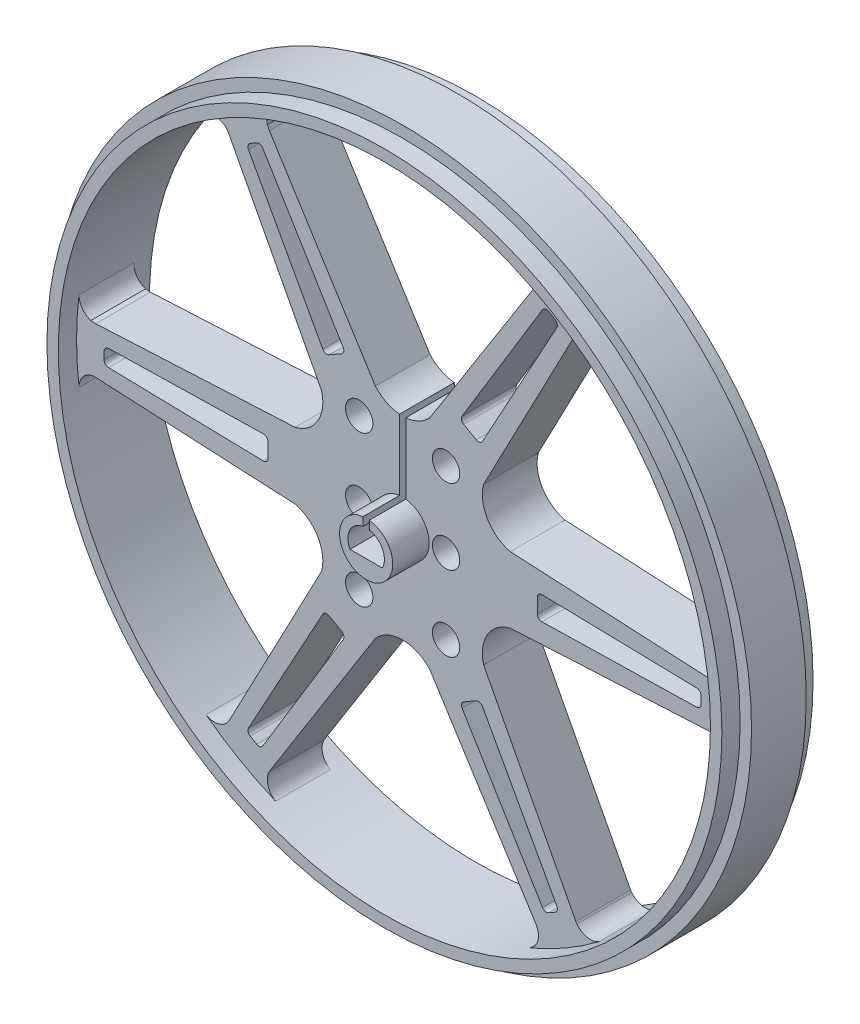
SolidWorks part; units mm, degrees
material "ABS"
ref_plane "Ön Düzlem" through (0, 0, 0) normal (0, 0, 1) x (1, 0, 0)
ref_plane "Üst Düzlem" through (0, 0, 0) normal (0, 1, 0) x (1, 0, 0)
ref_plane "Sağ Düzlem" through (0, 0, 0) normal (1, 0, 0) x (0, 0, -1)
sketch "Çizim1" plane through (0, 0, 0) normal (0, 0, 1) x (1, 0, 0)
  line L1 (-0.0047, 8.2114) -> (0.3453, 8.2114)
  line L2 (-0.0047, 8.2114) -> (-0.3547, 8.2115)
  line L3 (0.3453, 10.6198) -> (0.3453, 1.97)
  line L4 (-0.3399, 10.62) -> (-0.3443, 1.9701)
  line L5 (-1.771, -0.9293) -> (1.771, -0.9293)
  line L6 (33.6573, 2.4999) -> (33.8491, 2.5141)
  line L7 (33.6573, -2.4999) -> (33.8491, -2.5141)
  line L9 (18.994, -27.8979) -> (19.1072, -28.0642)
  line L16 (-33.6536, -2.5496) -> (-34.1903, -2.5903)
  line L17 (-33.6536, 2.5496) -> (-34.1903, 2.5903)
  line L18 (-19.3245, 28.3019) -> (-19.0457, 27.8638)
  line L19 (-14.8479, 30.8484) -> (-14.6079, 30.3879)
  line L21 (14.6633, 30.3602) -> (14.6637, 30.3599)
  line L24 (18.994, 27.8979) -> (18.9936, 27.8981)
  line L36 (-19.0457, 27.8638) -> (-8.8869, 8.5771)
  line L37 (-14.6079, 30.3879) -> (-2.985, 11.9466)
  line L39 (14.6633, 30.3602) -> (2.991, 11.9451)
  line L40 (18.994, 27.8979) -> (8.883, 8.5811)
  line L41 (33.6573, 2.4999) -> (11.8039, 3.6347)
  line L42 (33.6573, -2.4999) -> (11.8043, -3.6332)
  line L43 (8.8819, -8.5822) -> (18.994, -27.8979)
  line L44 (2.9911, -11.9832) -> (14.6637, -30.398)
  line L45 (-2.9849, -11.9847) -> (-14.6079, -30.426)
  line L46 (-8.8883, -8.5756) -> (-19.0457, -27.8638)
  line L47 (-11.8026, -3.6389) -> (-33.6536, -2.5496)
  line L48 (-11.8008, 3.6448) -> (-33.6536, 2.5496)
  line L49 (32.7268, 0.411) -> (32.7268, -0.411)
  line L50 (32.2379, 0.9109) -> (15.2736, 1.2886)
  line L51 (14.7625, 0.7887) -> (14.7625, -0.7887)
  line L52 (32.2379, -0.9109) -> (15.2736, -1.2886)
  line L53 (-32.7268, 0.411) -> (-32.7268, -0.411)
  line L54 (-32.2379, -0.9109) -> (-15.2736, -1.2886)
  line L55 (-32.2379, 0.9109) -> (-15.2736, 1.2886)
  line L56 (-14.7625, 0.7887) -> (-14.7625, -0.7887)
  line L57 (6.6982, 13.1791) -> (8.0643, 12.3903)
  line L58 (16.9078, 27.4634) -> (8.7528, 12.583)
  line L59 (16.0074, 28.5477) -> (16.7193, 28.1367)
  line L60 (15.3301, 28.3743) -> (6.5208, 13.8717)
  line L61 (16.0074, -28.5477) -> (16.7193, -28.1367)
  line L62 (15.3301, -28.3743) -> (6.5208, -13.8717)
  line L63 (6.6982, -13.1791) -> (8.0643, -12.3903)
  line L64 (16.9078, -27.4634) -> (8.7528, -12.583)
  line L65 (-6.6982, 13.1791) -> (-8.0643, 12.3903)
  line L66 (-16.0074, 28.5477) -> (-16.7193, 28.1367)
  line L67 (-16.9078, 27.4634) -> (-8.7528, 12.583)
  line L68 (-15.3301, 28.3743) -> (-6.5208, 13.8717)
  line L69 (-16.0074, -28.5477) -> (-16.7193, -28.1367)
  line L70 (-6.6982, -13.1791) -> (-8.0643, -12.3903)
  line L71 (-16.9078, -27.4634) -> (-8.7528, -12.583)
  line L72 (-15.3301, -28.3743) -> (-6.5208, -13.8717)
  circle A0 centre (0, 0) radius 38.25
  circle A1 centre (0, 0) radius 37
  circle A2 centre (0, 0) radius 35.75
  circle A3 centre (-4.7625, 8.25) radius 1.5
  circle A4 centre (4.7625, 8.25) radius 1.5
  circle A5 centre (4.7625, -8.25) radius 1.5
  circle A6 centre (-4.7625, -8.25) radius 1.5
  circle A7 centre (4.7625, 0) radius 1.5
  circle A8 centre (-4.7625, 0) radius 1.5
  arc A9 (-0.3443, 1.9701) -> (-1.771, -0.9293) centre (0, 0) ccw
  arc A10 (11.8039, 3.6347) -> (8.883, 8.5811) centre (12.739, 7.5225) cw
  arc A11 (-11.8008, 3.6448) -> (-8.8869, 8.5771) centre (-12.7477, 7.5311) ccw
  arc A12 (-11.8026, -3.6389) -> (-8.8883, -8.5756) centre (-12.748, -7.5256) cw
  arc A13 (11.8043, -3.6332) -> (8.8819, -8.5822) centre (12.739, -7.5225) ccw
  arc A14 (2.991, 11.9451) -> (0.3453, 10.6198) centre (0.0037, 14.6052) cw
  arc A15 (2.9911, -11.9832) -> (-2.9849, -11.9847) centre (0.0037, -14.6432) ccw
  arc A16 (-0.3399, 10.62) -> (-2.985, 11.9466) centre (0.0037, 14.6052) cw
  arc A17 (1.771, -0.9293) -> (0.3453, 1.97) centre (0, 0) ccw
  circle A18 centre (0, 0) radius 2.913
  arc A21 (32.2379, 0.9109) -> (32.7268, 0.411) centre (32.2268, 0.411) cw
  arc A22 (32.2379, -0.9109) -> (32.7268, -0.411) centre (32.2268, -0.411) ccw
  arc A23 (15.2736, -1.2886) -> (14.7625, -0.7887) centre (15.2625, -0.7887) cw
  arc A24 (15.2736, 1.2886) -> (14.7625, 0.7887) centre (15.2625, 0.7887) ccw
  arc A25 (-32.2379, 0.9109) -> (-32.7268, 0.411) centre (-32.2268, 0.411) ccw
  arc A26 (-32.2379, -0.9109) -> (-32.7268, -0.411) centre (-32.2268, -0.411) cw
  arc A27 (-15.2736, -1.2886) -> (-14.7625, -0.7887) centre (-15.2625, -0.7887) ccw
  arc A28 (-15.2736, 1.2886) -> (-14.7625, 0.7887) centre (-15.2625, 0.7887) cw
  arc A29 (6.5208, 13.8717) -> (6.6982, 13.1791) centre (6.9482, 13.6121) ccw
  arc A30 (8.7528, 12.583) -> (8.0643, 12.3903) centre (8.3143, 12.8233) cw
  arc A31 (16.9078, 27.4634) -> (16.7193, 28.1367) centre (16.4693, 27.7037) ccw
  arc A32 (15.3301, 28.3743) -> (16.0074, 28.5477) centre (15.7574, 28.1147) cw
  arc A33 (16.9078, -27.4634) -> (16.7193, -28.1367) centre (16.4693, -27.7037) cw
  arc A34 (15.3301, -28.3743) -> (16.0074, -28.5477) centre (15.7574, -28.1147) ccw
  arc A35 (8.7528, -12.583) -> (8.0643, -12.3903) centre (8.3143, -12.8233) ccw
  arc A36 (6.5208, -13.8717) -> (6.6982, -13.1791) centre (6.9482, -13.6121) cw
  arc A37 (-6.5208, 13.8717) -> (-6.6982, 13.1791) centre (-6.9482, 13.6121) cw
  arc A38 (-8.7528, 12.583) -> (-8.0643, 12.3903) centre (-8.3143, 12.8233) ccw
  arc A39 (-16.9078, 27.4634) -> (-16.7193, 28.1367) centre (-16.4693, 27.7037) cw
  arc A40 (-15.3301, 28.3743) -> (-16.0074, 28.5477) centre (-15.7574, 28.1147) ccw
  arc A41 (-16.9078, -27.4634) -> (-16.7193, -28.1367) centre (-16.4693, -27.7037) ccw
  arc A42 (-15.3301, -28.3743) -> (-16.0074, -28.5477) centre (-15.7574, -28.1147) cw
  arc A43 (-6.5208, -13.8717) -> (-6.6982, -13.1791) centre (-6.9482, -13.6121) ccw
  arc A44 (-8.7528, -12.583) -> (-8.0643, -12.3903) centre (-8.3143, -12.8233) cw
  arc A45 (35.4777, 4.404) -> (33.8491, 2.5141) centre (33.6154, 4.3621) cw
  arc A46 (35.4777, -4.404) -> (33.8491, -2.5141) centre (33.6154, -4.3621) ccw
  arc A47 (-35.4777, -4.404) -> (-34.1903, -2.5903) centre (-33.6154, -4.3621) cw
  arc A48 (-35.4777, 4.404) -> (-34.1903, 2.5903) centre (-33.6154, 4.3621) ccw
  arc A49 (13.9249, 32.9266) -> (14.6637, 30.3599) centre (13.0463, 31.284) cw
  arc A50 (21.5528, 28.5226) -> (18.9936, 27.8981) centre (20.5854, 26.9308) ccw
  arc A51 (-21.5528, 28.5226) -> (-19.3245, 28.3019) centre (-20.5854, 26.9308) cw
  arc A52 (-13.9249, 32.9266) -> (-14.8479, 30.8484) centre (-13.0379, 31.2886) ccw
  arc A53 (21.5528, -28.5226) -> (19.1072, -28.0642) centre (20.5854, -26.9308) cw
  arc A54 (13.9249, -32.9266) -> (14.6637, -30.398) centre (13.03, -31.2929) ccw
  arc A55 (-13.9249, -32.9266) -> (-14.6079, -30.426) centre (-12.9758, -31.3238) cw
  arc A56 (-21.5528, -28.5226) -> (-19.0457, -27.8638) centre (-20.6393, -26.8992) ccw
  point P30 (33.6573, 0)
  point P34 (-16.8454, 29.1772)
  point P41 (-16.8268, -29.1449)
  point P43 (16.8232, 29.1386)
  point P47 (-33.6536, 0)
  point P48 (1.3819, -0.9475)
  point P49 (33.6573, 0)
  point P54 (16.8726, -29.2243)
  point P100 (32.7268, 0)
  point P104 (14.7625, 0)
  point P106 (32.7268, 0.9)
  point P109 (32.7268, -0.9)
  point P112 (14.7625, -1.3)
  point P115 (14.7625, 1.3)
  dimension "D1" = 2
  dimension "D2" = 0.5
extrude "Yükseklik-Ekstrüzyon5" add sketch "Çizim1" along normal blind 5 and the other way blind 5 contours A1 A2 region at (-35.9535, 0, 0)
extrude "Yükseklik-Ekstrüzyon6" add sketch "Çizim1<13>" along normal blind 3 and the other way blind 3 contours A0 A1 region at (-37.1681, 0, 0)
sketch "Çizim1<13>" plane through (0, 0, 0) normal (0, 0, 1) x (1, 0, 0) same geometry as "Çizim1"
extrude "Yükseklik-Ekstrüzyon7" add sketch "Çizim1<14>" along normal blind 3 and the other way blind 3 contours A56 A2 A55 L45 A15 L44 A54 A53 L9 L43 A13 L42 L7 A46 A45 L6 L41 A10 L40 L24 A50 A49 L21 L39 A14 L3 A17 L5 A9 L4 A16 L37 L19 A52 A51 L18 L36 A11 L48 L17 A48 A47 L16 L47 region at (-0.6267, 9.4156, 0)
sketch "Çizim1<14>" plane through (0, 0, 0) normal (0, 0, 1) x (1, 0, 0) same geometry as "Çizim1"
extrude "Yükseklik-Ekstrüzyon8" add sketch "Çizim1<17>" along normal blind 7 and the other way blind 3 contours L4 A18 L3 A17 L5 A9 region at (2.117, 1.8793, 0)
sketch "Çizim1<17>" plane through (0, 0, 0) normal (0, 0, 1) x (1, 0, 0) same geometry as "Çizim1"
